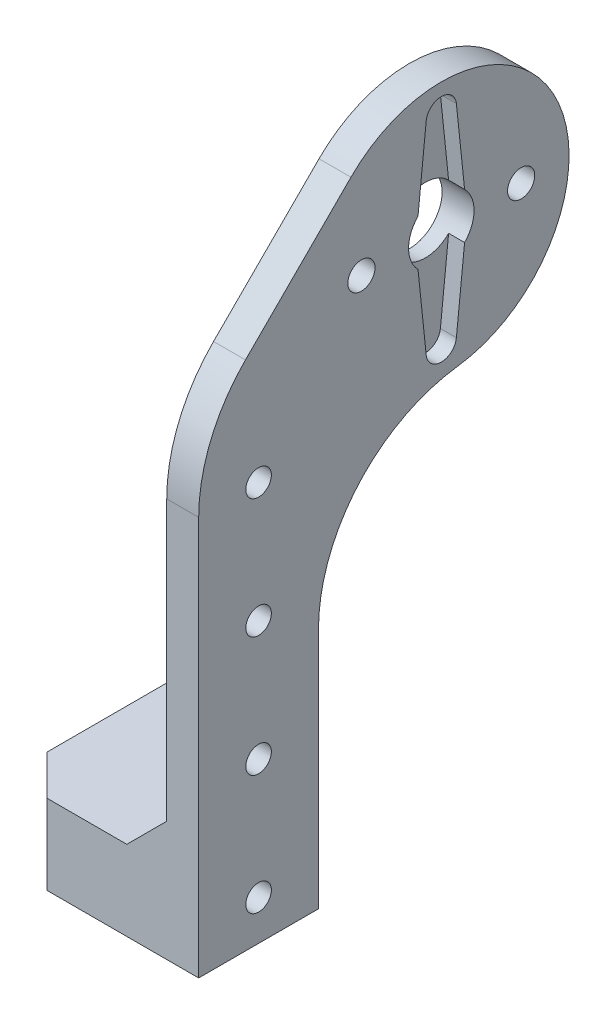
SolidWorks part; units mm, degrees
ref_plane "Front Plane" through (0, 0, 0) normal (0, 0, 1) x (1, 0, 0)
ref_plane "Top Plane" through (0, 0, 0) normal (0, 1, 0) x (1, 0, 0)
ref_plane "Right Plane" through (0, 0, 0) normal (1, 0, 0) x (0, 0, -1)
sketch "Sketch1" plane through (0, 0, 0) normal (1, 0, 0) x (0, 0, -1)
  circle A0 centre (0, 0) radius 16
  dimension "D1" = 32
extrude "Boss-Extrude1" add sketch "Sketch1" along normal blind 4
sketch "Sketch5" plane through (4, 0, 0) normal (1, 0, 0) x (0, 0, -1)
  line L0 (0, 0) -> (0, 50000) construction
  line L1 (-1.8897, 12.6976) -> (-2.933, 2.7198)
  line L2 (-2.933, -2.7198) -> (-1.8897, -12.6976)
  line L3 (1.8897, -12.6976) -> (2.933, -2.7198)
  line L4 (2.933, 2.7198) -> (1.8897, 12.6976)
  line L5 (1.2496, 0) -> (50001.2496, 0) construction
  arc A0 (-2.933, 2.7198) -> (-2.933, -2.7198) centre (0, 0) ccw
  arc A1 (1.8897, 12.6976) -> (-1.8897, 12.6976) centre (0, 12.5) ccw
  arc A2 (-1.8897, -12.6976) -> (1.8897, -12.6976) centre (0, -12.5) ccw
  circle A3 centre (0, 0) radius 3.2 construction
  arc A4 (2.933, -2.7198) -> (2.933, 2.7198) centre (0, 0) ccw
  dimension "D1" = 1.9
  dimension "D2" = 4
  dimension "D4" = 6.4
  dimension "D3" = 25
extrude "Cut-Extrude2" cut sketch "Sketch5" against normal blind 2
sketch "Sketch3" plane through (4, 0, 0) normal (1, 0, 0) x (0, 0, -1)
  circle A0 centre (0, 0) radius 4.1
  dimension "D1" = 8.2
extrude "Cut-Extrude1" cut sketch "Sketch3" against normal through all
hole_wizard "CSK for M3 Countersunk Flat Head Screw1" positions "Sketch8" profile "Sketch7" countersink size "M3" standard "ISO" end condition through all
sketch "Sketch8" plane through (0, 0, 0) normal (-1, 0, 0) x (0, 0, 1)
  line L0 (0, 0) -> (0, 50000) construction
  line L1 (0, 0) -> (50000, 0) construction
  point P0 (-10, 0)
  point P2 (10, 0)
  dimension "D1" = 20
sketch "Sketch7" plane through (0, 0, -10) normal (0, 1, 0) x (0, 0, 1)
  line L0 (0, 0) -> (0, 28)
  line L1 (0, 28) -> (1.7, 28)
  line L2 (1.7, 28) -> (1.7, 1.45)
  line L3 (1.7, 1.45) -> (3.15, 0)
  line L5 (3.15, 0) -> (0, 0)
  line L6 (-1.7, 1.45) -> (-3.15, 0) construction
  line L11 (0, -6.35) -> (0, 107.95) construction
  dimension "Thru Hole Dia." = 3.4
  dimension "Thru Hole Depth" = 28
  dimension "Near C'Sink Dia." = 6.3
  dimension "Near C'Sink Angle" = 90
sketch "Sketch9" plane through (0, 0, 0) normal (1, 0, 0) x (0, 0, -1)
  line L0 (-30.3816, -7.7542) -> (-30.3816, -66)
  line L1 (-30.3816, -66) -> (-15.3816, -66)
  line L2 (-15.3816, -66) -> (-15.3816, -16)
  line L3 (-15.3816, -16) -> (0, -16)
  line L4 (-30.3816, -7.7542) -> (-11.3137, 11.3137)
  circle A0 centre (0, 0) radius 16 construction
  arc A1 (-11.3137, 11.3137) -> (0, -16) centre (0, 0) ccw
  dimension "D1" = 15
  dimension "D2" = 45
  dimension "D3" = 50
extrude "Boss-Extrude3" add sketch "Sketch9" along normal up to surface (4 mm away) up to face at (4, 0, -8.3)
fillet "Fillet3" radius 20 2 edges at (2, -7.7542, 30.3816) (2, -16, 15.3816)
sketch "Sketch11" plane through (0, -66, 0) normal (0, -1, 0) x (1, 0, 0)
  line L0 (0, 15.3816) -> (-10, 15.3816)
  line L1 (-10, 15.3816) -> (-10, 0)
  line L2 (-10, 0) -> (-20, 0)
  line L3 (-20, 0) -> (-20, 30.3816)
  line L4 (-20, 30.3816) -> (0, 30.3816)
  line L5 (0, 30.3816) -> (0, 15.3816)
  dimension "D1" = 10
  dimension "D2" = 20
  dimension "D3" = 30.3816
extrude "Boss-Extrude4" add sketch "Sketch11" against normal blind 10
chamfer "Chamfer1" distance 5 angle 45 3 edges at (-10, -61, 15.3816) (-20, -61, 30.3816)
sketch "Sketch12" plane through (-10, 0, 0) normal (1, 0, 0) x (0, 0, -1)
  line L0 (-6.9559, -66) -> (-3.3162, -56)
  line L1 (0, -66) -> (-10.3816, -66) construction
  line L2 (0, -56) -> (-10.3816, -56) construction
  line L3 (-3.3162, -56) -> (0, -56)
  line L4 (0, -56) -> (0, -66)
  line L5 (0, -66) -> (-6.9559, -66)
  dimension "D1" = 6.9559
  dimension "D2" = 3.3162
extrude "Cut-Extrude5" cut sketch "Sketch12" against normal through all
sketch "Sketch10" plane through (4, 0, 0) normal (1, 0, 0) x (0, 0, -1)
  line L0 (-22.8816, -66) -> (-22.8816, 49934) construction
  line L1 (-30.3816, -66) -> (-15.3816, -66) construction
  circle A0 centre (-22.8816, -16) radius 1.6
  circle A1 centre (-22.8816, -31) radius 1.6
  circle A2 centre (-22.8816, -46) radius 1.6
  circle A3 centre (-22.8816, -61) radius 1.6
  point P4 (-22.8816, -66)
  dimension "D1" = 3.2
  dimension "D2" = 15
  dimension "D3" = 15
  dimension "D4" = 15
  dimension "D5" = 5
extrude "Cut-Extrude4" cut sketch "Sketch10" against normal through all
